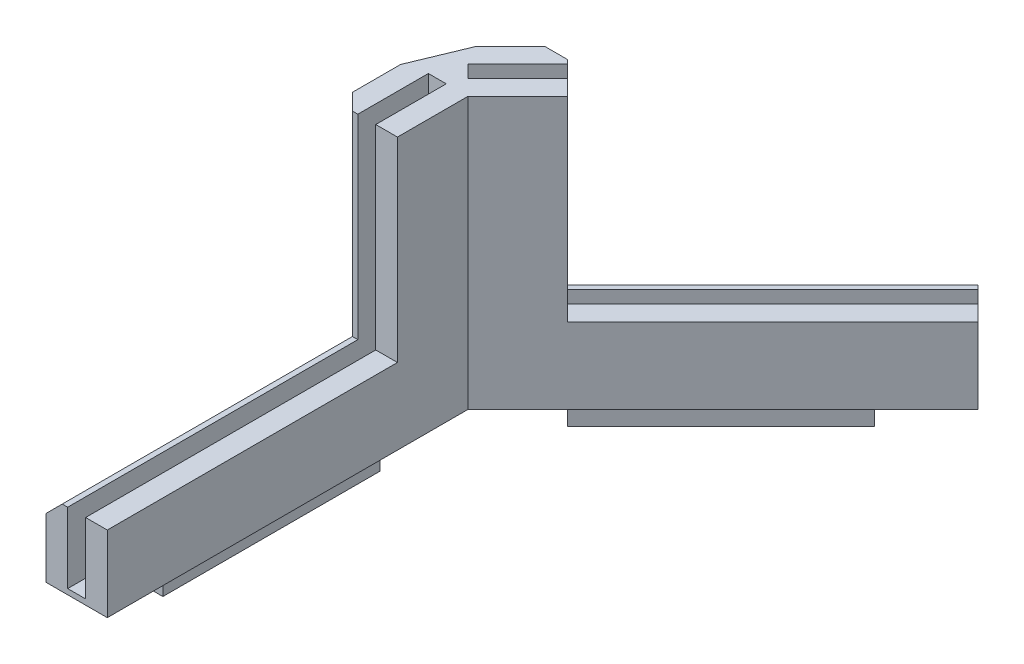
SolidWorks part; units mm, degrees
ref_plane "Front Plane" through (0, 0, 0) normal (0, 0, 1) x (1, 0, 0)
ref_plane "Top Plane" through (0, 0, 0) normal (0, 1, 0) x (1, 0, 0)
ref_plane "Right Plane" through (0, 0, 0) normal (1, 0, 0) x (0, 0, -1)
sketch "Sketch2" plane through (0, 0, 0) normal (0, 1, 0) x (1, 0, 0)
  line L0 (-1.7, -2) -> (-1.7, -15)
  line L1 (-1.7, -15) -> (-5.7, -15)
  line L2 (-5.7, -15) -> (-5.7, -2)
  line L3 (-5.7, -2) -> (-9, -2)
  line L4 (-9, -2) -> (-9, -15)
  line L5 (-9, -15) -> (-13, -15)
  line L7 (-13, -15) -> (-13, 2.6806)
  line L9 (-1.7, -2) -> (-13, 2.6806)
extrude "Boss-Extrude1" add sketch "Sketch2" along normal blind 50
sketch "Sketch3" plane through (0, 0, 2) normal (0, 0, 1) x (1, 0, 0)
  line L0 (-9, 0) -> (-9, 1)
  line L1 (-9, 50) -> (-9, 0) construction
  line L2 (-5.7, 0) -> (-5.7, 1)
  line L3 (-5.7, 50) -> (-5.7, 0) construction
  line L4 (-5.7, 1) -> (-9, 1)
  line L5 (-9, 0) -> (-5.7, 0)
extrude "Boss-Extrude2" add sketch "Sketch3" along normal up to vertex (13 mm away) up to point (-9, 0, 15)
sketch "Sketch5" plane through (0, 0, 15) normal (0, 0, 1) x (1, 0, 0)
  line L0 (-13, 0) -> (-1.7, 0)
  line L1 (-1.7, 50) -> (-1.7, 0) construction
  line L2 (-13, 0) -> (-1.7, 0) construction
  line L3 (-1.7, 0) -> (-1.7, 14)
  line L4 (-13, 0) -> (-13, 14)
  line L5 (-13, 50) -> (-13, 0) construction
  line L6 (-9, 1) -> (-9, 14)
  line L7 (-9, 50) -> (-9, 1) construction
  line L8 (-5.7, 1) -> (-5.7, 14)
  line L9 (-5.7, 50) -> (-5.7, 1) construction
  line L10 (-13, 14) -> (-9, 14)
  line L11 (-9, 1) -> (-5.7, 1)
  line L12 (-5.7, 14) -> (-1.7, 14)
extrude "Boss-Extrude3" add sketch "Sketch5" along normal blind 53.5
sketch "Sketch6" plane through (0, 0, 0) normal (0, -1, 0) x (-1, 0, 0)
  line L0 (4.95, -15) -> (9.75, -15)
  line L1 (13, -68.5) -> (1.7, -68.5) construction
  line L2 (13, -68.5) -> (9.75, -68.5) construction
  line L3 (1.7, -68.5) -> (4.95, -68.5) construction
  line L4 (9.75, -68.5) -> (9.75, -55) construction
  line L7 (4.95, -55) -> (9.75, -55)
  line L13 (9.75, -55) -> (9.75, -15)
  line L14 (4.95, -55) -> (4.95, -15)
  line L15 (4.95, -55) -> (4.95, -68.5) construction
extrude "Boss-Extrude4" add sketch "Sketch6" along normal blind 5
ref_plane "Plane1" through (-0.9561, 0, 2.3081) normal (0.3827, 0, -0.9239) x (-0.9239, 0, -0.3827)
mirror "Mirror1" about plane through (-0.9561, 0, 2.3081) normal (0.3827, 0, -0.9239) of bodies 117
fillet "Chamfer1" radius 14 1 edges at (-13, 25, -2.6806) type face fillet profile chamfer first side face at (7.9447, 21.3333, -23.6254) second side face at (-13, 21.3333, 26.9398)
chamfer "Chamfer2" distance 3 angle 45 4 edges at (-13, 14, 41.75) (-13, 32, 15) (-0.4979, 32, -15.1827) (18.4171, 14, -34.0978)
